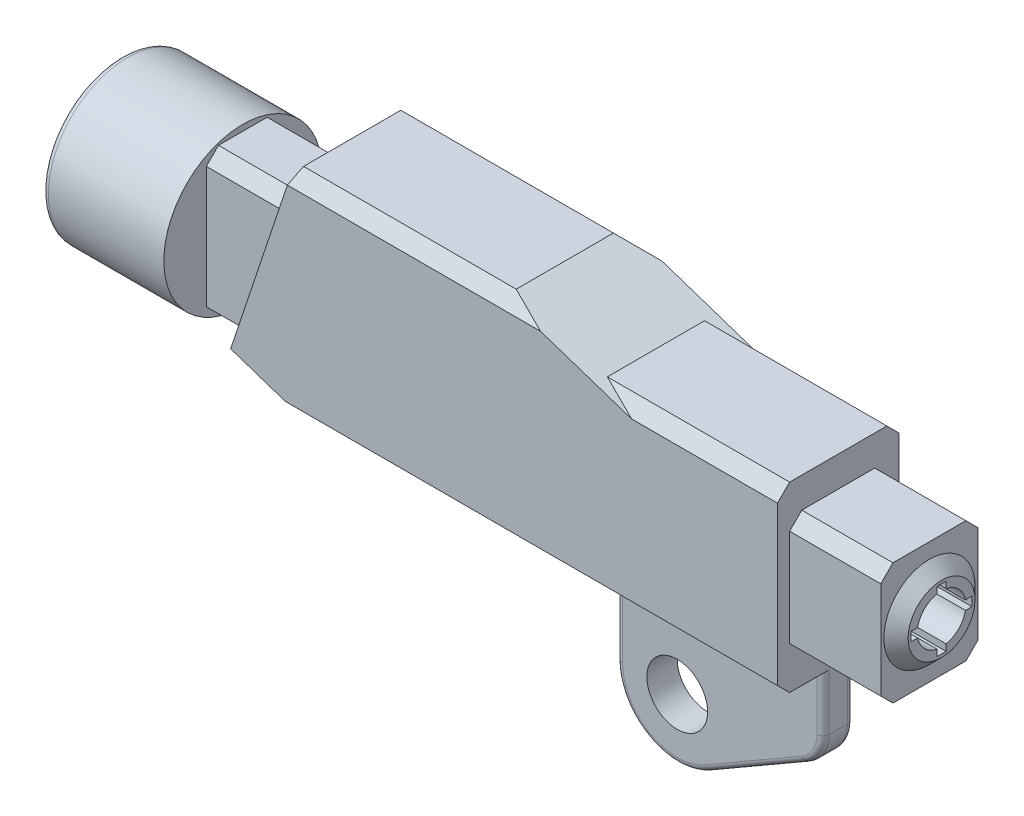
SolidWorks part; units mm, degrees
material "6061 Alloy"
ref_plane "Front Plane" through (0, 0, 0) normal (0, 0, 1) x (1, 0, 0)
ref_plane "Top Plane" through (0, 0, 0) normal (0, 1, 0) x (1, 0, 0)
ref_plane "Right Plane" through (0, 0, 0) normal (1, 0, 0) x (0, 0, -1)
sketch "Sketch1" plane through (0, 0, 0) normal (1, 0, 0) x (0, 0, -1)
  circle A0 centre (0, 0) radius 13
  dimension "D1" = 26
extrude "Boss-Extrude1" add sketch "Sketch1" along normal blind 20
sketch "Sketch2" plane through (0, 0, 0) normal (-1, 0, 0) x (0, 0, 1)
  circle A0 centre (0, 0) radius 4
  dimension "D1" = 8
extrude "Cut-Extrude1" cut sketch "Sketch2" against normal blind 15
sketch "Sketch3" plane through (20, 0, 0) normal (1, 0, 0) x (0, 0, -1)
  line L1 (-6, -12) -> (6, -12)
  line L2 (-6, -12) -> (-6, 12)
  line L3 (-6, 12) -> (6, 12)
  line L4 (6, -12) -> (6, 12)
  line L5 (-6, -12) -> (6, 12) construction
  line L6 (-6, 12) -> (6, -12) construction
  point P0 (0, 0)
  dimension "D1" = 12
  dimension "D2" = 24
extrude "Boss-Extrude2" add sketch "Sketch3" along normal blind 70
chamfer "Chamfer1" distance 2 angle 45 4 edges at (55, -12, 6) (55, -12, -6) (55, 12, -6) (55, 12, 6)
sketch "Sketch4" plane through (0, 0, 0) normal (0, 0, 1) x (1, 0, 0)
  line L0 (28, -10) -> (38, 20)
  line L1 (20, -10) -> (90, -10) construction
  line L2 (38, 20) -> (73, 20)
  line L3 (73, 20) -> (88, 15)
  line L4 (88, 15) -> (118, 15)
  line L5 (28, -10) -> (43, -15)
  line L6 (43, -15) -> (118, -15)
  line L7 (118, -15) -> (118, 15)
  line L8 (20, -13) -> (20, 13) construction
  dimension "D1" = 35
  dimension "D2" = 30
  dimension "D3" = 15
  dimension "D4" = 30
  dimension "D5" = 5
  dimension "D6" = 5
  dimension "D7" = 8
extrude "Boss-Extrude3" add sketch "Sketch4" along normal mid plane 20
chamfer "Chamfer2" distance 2 angle 45 6 edges at (103, 15, -10) (103, 15, 10) (80.5, -15, -10) (80.5, -15, 10) (55.5, 20, -10) (55.5, 20, 10)
ref_axis "Axis1" through (170.5706, 0, 0) along (-1, 0, 0)
sketch "Sketch5" plane through (118, 0, 0) normal (1, 0, 0) x (0, 0, -1)
  line L1 (-8, -10) -> (8, -10)
  line L2 (-8, -10) -> (-8, 10)
  line L3 (-8, 10) -> (8, 10)
  line L4 (8, -10) -> (8, 10)
  line L5 (-8, -10) -> (8, 10) construction
  line L6 (-8, 10) -> (8, -10) construction
  point P0 (0, 0)
  dimension "D1" = 16
  dimension "D2" = 20
extrude "Boss-Extrude4" add sketch "Sketch5" along normal blind 15
chamfer "Chamfer3" distance 2 angle 45 4 edges at (125.5, -10, 8) (125.5, -10, -8) (125.5, 10, -8) (125.5, 10, 8)
sketch "Sketch6" plane through (133, 0, 0) normal (1, 0, 0) x (0, 0, -1)
  circle A0 centre (0, 0) radius 7.5
  dimension "D1" = 15
extrude "Boss-Extrude5" add sketch "Sketch6" along normal blind 2
sketch "Sketch7" plane through (135, 0, 0) normal (1, 0, 0) x (0, 0, -1)
  line L0 (5, 0.75) -> (5, -0.75)
  line L1 (-0.75, 5) -> (0.75, 5)
  line L2 (-0.75, 5) -> (-0.75, 3)
  line L3 (-0.75, 3) -> (0.75, 3)
  line L4 (0.75, 5) -> (0.75, 3)
  line L5 (-0.75, 5) -> (0.75, 3) construction
  line L6 (-0.75, 3) -> (0.75, 5) construction
  line L7 (5, -0.75) -> (3, -0.75)
  line L8 (5, 0.75) -> (3, 0.75)
  line L9 (0.75, -5) -> (-0.75, -5)
  line L10 (-0.75, -5) -> (-0.75, -3)
  line L11 (0.75, -5) -> (0.75, -3)
  line L12 (-5, -0.75) -> (-5, 0.75)
  line L13 (-5, 0.75) -> (-3, 0.75)
  line L14 (-5, -0.75) -> (-3, -0.75)
  circle A0 centre (0, 0) radius 4
  point P3 (0, 4)
  point P23 (0, 0)
  dimension "D1" = 8
  dimension "D2" = 1.5
  dimension "D3" = 2
  dimension "D4" = 4
extrude "Cut-Extrude2" cut sketch "Sketch7" against normal blind 20 contours L2 A0 L4 L3 | A0 L13 L12 L14 | A0 L4 L1 L2 | A0 L7 L0 L8 | A0 L10 L9 L11 | L4 A0 L2 L3 region at (135, 0, -4.488) region at (135, -0.1047, 0) region at (135, 4.488, 0) region at (135, 3.4884, 0) region at (135, -4.488, 0) region at (135, 0, 4.488)
chamfer "Chamfer4" distance 2 angle 45 1 edges at (135, 7.5, 0)
sketch "Sketch8" plane through (0, 0, 0) normal (0, 0, 1) x (1, 0, 0)
  line L0 (84, -15) -> (84, -30)
  line L1 (118, -15) -> (43, -15) construction
  line L2 (99, -38.6603) -> (115, -29.4226)
  line L3 (118, -15) -> (43, -15)
  line L5 (118, -15) -> (118, -24.2265)
  arc A0 (84, -30) -> (99, -38.6603) centre (94, -30) ccw
  arc A1 (115, -29.4226) -> (118, -24.2265) centre (112, -24.2265) ccw
  circle A2 centre (94, -30) radius 5
  dimension "D2" = 10
  dimension "D4" = 6
  dimension "D6" = 10
  dimension "D1" = 15
  dimension "D3" = 16
  dimension "D5" = 34
extrude "Boss-Extrude6" add sketch "Sketch8" along normal mid plane 5 contours L2 A1 L5 L3 L0 A0 A2 region at (100.2527, -25.0241, 0)
fillet "Fillet1" radius 1 1 edges at (0, 0, -13)
fillet "Fillet2" radius 1 10 edges at (84, -22.5, -2.5) (89, -38.6603, -2.5) (107, -34.0415, -2.5) (117.1962, -27.2265, -2.5) (84, -22.5, 2.5) (89, -38.6603, 2.5) (118, -19.6132, 2.5) (117.1962, -27.2265, 2.5) (118, -19.6132, -2.5) (107, -34.0415, 2.5)
